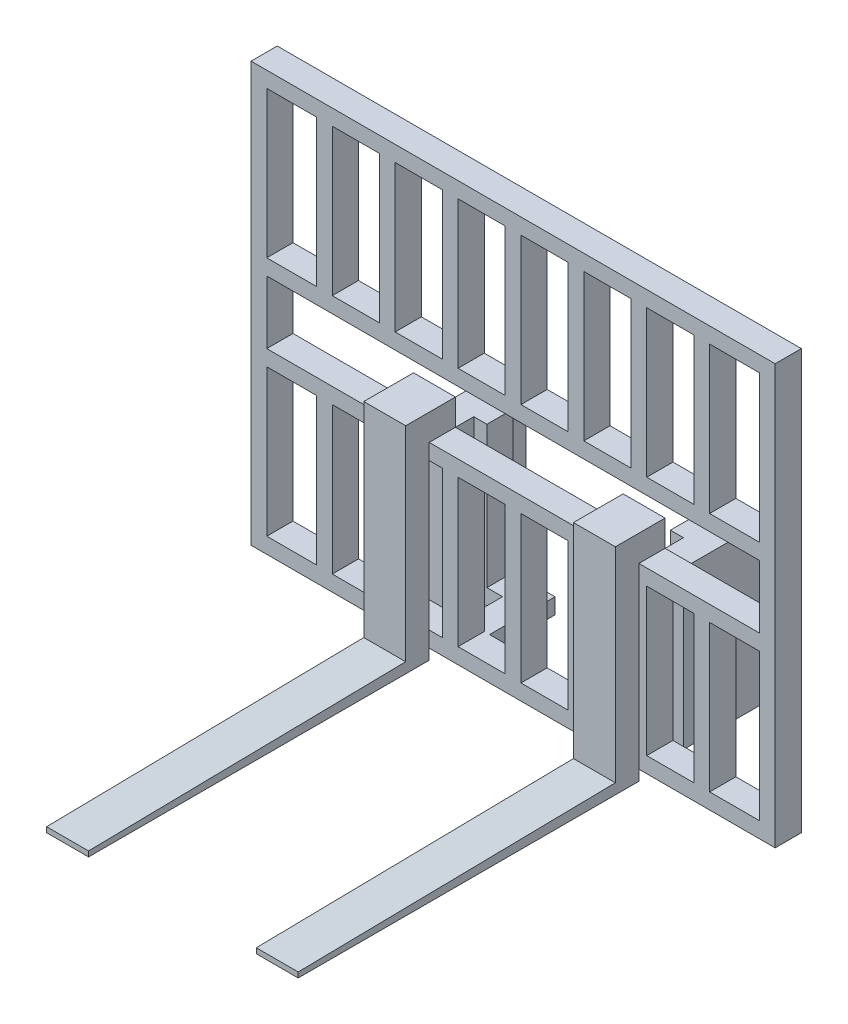
SolidWorks part; units mm, degrees
ref_plane "前基準面" through (0, 0, 0) normal (0, 0, 1) x (1, 0, 0)
ref_plane "上基準面" through (0, 0, 0) normal (0, 1, 0) x (1, 0, 0)
ref_plane "右基準面" through (0, 0, 0) normal (1, 0, 0) x (0, 0, -1)
sketch "草圖1" plane through (0, 0, 0) normal (0, 0, 1) x (1, 0, 0)
  line L1 (-500, 750) -> (500, 750)
  line L2 (-500, 750) -> (-500, -50)
  line L3 (-500, -50) -> (500, -50)
  line L4 (500, 750) -> (500, -50)
  line L5 (-500, 750) -> (500, -50) construction
  line L6 (-500, -50) -> (500, 750) construction
  line L7 (-470, 720) -> (-470, 440)
  line L8 (-470, -20) -> (470, -20)
  line L9 (470, 720) -> (470, 440)
  line L10 (-470, 720) -> (470, 720)
  line L11 (470, 350) -> (-470, 350) construction
  line L12 (470, 410) -> (-470, 410)
  line L13 (470, 290) -> (-470, 290)
  line L14 (470, 440) -> (375, 440)
  line L15 (470, 260) -> (-470, 260)
  line L16 (0, 720) -> (0, 440) construction
  line L17 (-15, 720) -> (-15, 440)
  line L18 (15, 720) -> (15, 440)
  line L19 (120, 720) -> (120, 440) construction
  line L20 (240, 720) -> (240, 440) construction
  line L21 (360, 720) -> (360, 440) construction
  line L22 (105, 720) -> (105, 440)
  line L23 (225, 720) -> (225, 440)
  line L24 (345, 720) -> (345, 440)
  line L25 (135, 720) -> (135, 440)
  line L26 (255, 720) -> (255, 440)
  line L27 (375, 720) -> (375, 440)
  line L28 (-375, 720) -> (-375, 440)
  line L29 (-345, 720) -> (-345, 440)
  line L30 (-255, 720) -> (-255, 440)
  line L31 (-225, 720) -> (-225, 440)
  line L32 (-135, 720) -> (-135, 440)
  line L33 (-105, 720) -> (-105, 440)
  line L34 (375, -20) -> (375, 260)
  line L35 (345, -20) -> (345, 260)
  line L36 (255, -20) -> (255, 260)
  line L37 (225, -20) -> (225, 260)
  line L38 (135, -20) -> (135, 260)
  line L39 (105, -20) -> (105, 260)
  line L40 (15, -20) -> (15, 260)
  line L41 (-15, -20) -> (-15, 260)
  line L42 (-105, -20) -> (-105, 260)
  line L43 (-135, -20) -> (-135, 260)
  line L44 (-225, -20) -> (-225, 260)
  line L45 (-255, -20) -> (-255, 260)
  line L46 (-375, -20) -> (-375, 260)
  line L47 (-345, -20) -> (-345, 260)
  line L48 (-375, 440) -> (-470, 440)
  line L49 (470, 440) -> (-470, 440) construction
  line L50 (-255, 440) -> (-345, 440)
  line L51 (-135, 440) -> (-225, 440)
  line L52 (-15, 440) -> (-105, 440)
  line L53 (105, 440) -> (15, 440)
  line L54 (225, 440) -> (135, 440)
  line L55 (345, 440) -> (255, 440)
  line L56 (470, 410) -> (470, -20)
  line L57 (470, 720) -> (470, -20) construction
  line L58 (-470, 410) -> (-470, 290)
  line L59 (-470, 720) -> (-470, -20) construction
  line L60 (-470, 260) -> (-470, -20)
  point P0 (0, 350)
  dimension "D2" = 1000
  dimension "D3" = 800
  dimension "D11" = 4
  dimension "D4" = 30
  dimension "D5" = 60
  dimension "D6" = 60
  dimension "D7" = 30
  dimension "D8" = 30
  dimension "D9" = 15
  dimension "D10" = 15
  dimension "D12" = 15
  dimension "D13" = 15
extrude "填料-伸長1" add sketch "草圖1" along normal blind 50 contours L4 L1 L2 L3 L60 L15 L13 L58 L12 L56 L8 L24 L55 L26 L23 L54 L25 | L35 L8 L34 L15 | L37 L8 L36 L15 | L39 L8 L38 L15 | L41 L8 L40 L15 | L43 L8 L42 L15 | L45 L8 L44 L15 | L8 L47 L15 L46 region at (0, 411.5847, 0) region at (-360, 120, 0) region at (-240, 120, 0) region at (-120, 120, 0) region at (0, 120, 0) region at (120, 120, 0) region at (240, 120, 0) region at (360, 120, 0)
sketch "草圖2" plane through (0, 0, 0) normal (1, 0, 0) x (0, 0, -1)
  line L0 (-50, 410) -> (-50, 290) construction
  line L1 (0, 290) -> (-50, 290)
  line L2 (0, 290) -> (0, 340)
  line L3 (0, 340) -> (-50, 340)
  line L4 (-50, 290) -> (-50, 340)
  line L5 (-50, -50) -> (0, -50) construction
  line L6 (-50, 340) -> (-94.8893, 340)
  line L7 (-50, 340) -> (-50, -70)
  line L8 (-50, -70) -> (-94.8893, -70)
  line L9 (-94.8893, 340) -> (-94.8893, -50)
  line L10 (-94.8893, -70) -> (-700, -70)
  line L12 (0, 750) -> (0, -50) construction
  line L15 (-700, -60) -> (-94.8893, -50)
  line L16 (-700, -60) -> (-700, -70)
  dimension "D1" = 50
  dimension "D2" = 20
  dimension "D3" = 700
extrude "填料-伸長2" add sketch "草圖2" along normal mid plane 80 from offset 200 contours L4 L1 L2 L3 | L10 L8 L7 L4 L6 L9 region at (0, 315, 25) region at (0, 110, 57.6851) offset against normal yes
mirror "鏡射1" about plane through (0, 0, 0) normal (1, 0, 0) of "填料-伸長2"
sketch "草圖3" plane through (0, -50, 0) normal (0, -1, 0) x (1, 0, 0)
  line L0 (0, 0) -> (-250, 0)
  line L1 (-500, 0) -> (500, 0) construction
  line L3 (-250, -25) -> (-200, -25)
  line L4 (-250, -25) -> (-250, -175)
  line L5 (-250, -175) -> (-200, -175)
  line L6 (-200, -25) -> (-200, -175)
  line L7 (-175, -125) -> (-225, -125)
  line L8 (-175, -125) -> (-175, -75)
  line L9 (-175, -75) -> (-225, -75)
  line L10 (-225, -125) -> (-225, -75)
  line L11 (-175, -125) -> (-225, -75) construction
  line L12 (-175, -75) -> (-225, -125) construction
  line L13 (-175, -125) -> (-95, -125)
  line L14 (-175, -125) -> (-175, -75)
  line L15 (-175, -75) -> (-95, -75)
  line L16 (-95, -125) -> (-95, -75)
  line L17 (-95, -75) -> (-145, -75)
  line L18 (-95, -75) -> (-95, 0)
  line L19 (-95, 0) -> (-145, 0)
  line L20 (-145, -75) -> (-145, 0)
  point P9 (-200, -100)
  point P14 (-225, -100)
  point P15 (-225, -25)
  dimension "D1" = 250
  dimension "D2" = 50
  dimension "D3" = 150
  dimension "D4" = 25
  dimension "D5" = 50
  dimension "D6" = 80
  dimension "D7" = 50
extrude "填料-伸長3" add sketch "草圖3" against normal up to surface (30 mm away) contours L20 L15 L18 L0 | L13 L16 L15 L8 region at (-120, -50, -37.5) region at (-135, -50, -100) up to face at (-60, -20, 25)
extrude "填料-伸長4" add sketch "草圖3<3>" against normal blind 300 contours L7 L10 L9 L6 L3 L4 L5 | L8 L9 L6 L7 | L10 L7 L6 L9 region at (-187.5, -50, -100) region at (-227.5, -50, -100) region at (-212.5, -50, -100)
sketch "草圖3<3>" plane through (0, -50, 0) normal (0, -1, 0) x (1, 0, 0) same geometry as "草圖3"
mirror "鏡射2" about plane through (0, 0, 0) normal (1, 0, 0) of "填料-伸長3", "填料-伸長4"
